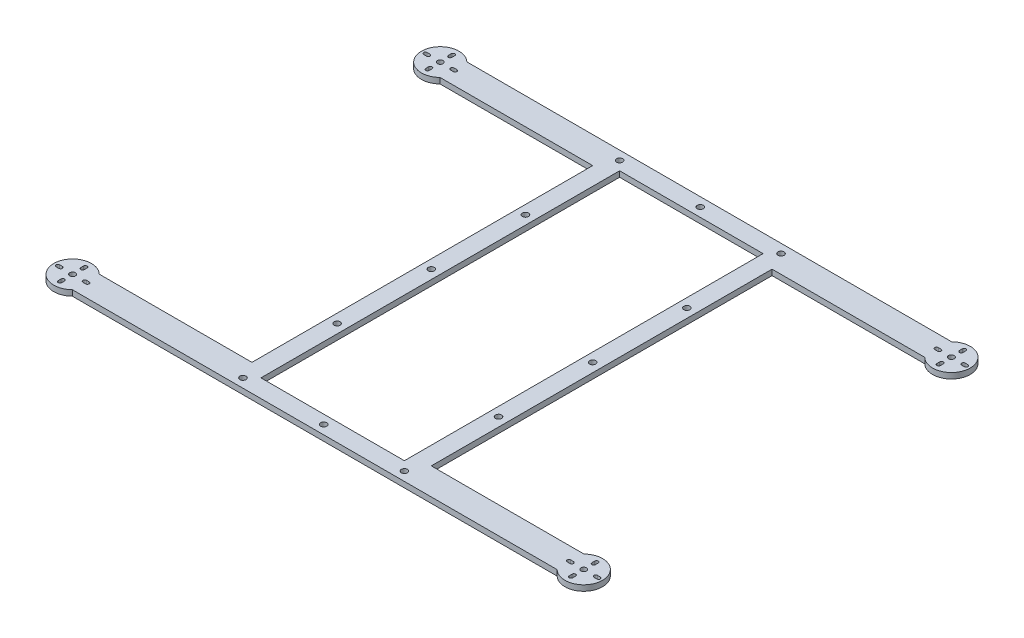
SolidWorks part; units mm, degrees
ref_plane "Front Plane" through (0, 0, 0) normal (0, 0, 1) x (1, 0, 0)
ref_plane "Top Plane" through (0, 0, 0) normal (0, 1, 0) x (1, 0, 0)
ref_plane "Right Plane" through (0, 0, 0) normal (1, 0, 0) x (0, 0, -1)
sketch "Sketch1" plane through (0, 0, 0) normal (0, 1, 0) x (1, 0, 0)
  line L1 (-63.5, 139.7) -> (63.5, 139.7)
  line L2 (-63.5, 120.65) -> (-63.5, -120.65)
  line L3 (-63.5, -139.7) -> (63.5, -139.7)
  line L4 (63.5, 120.65) -> (63.5, -120.65)
  line L5 (63.5, 139.7) -> (180.975, 139.7)
  line L7 (63.5, 120.65) -> (180.975, 120.65)
  line L8 (180.975, 139.7) -> (180.975, 120.65)
  line L14 (0, 0) -> (0, 187.5455) construction
  line L17 (0, 0) -> (-239.6804, 0) construction
  line L21 (0, 0) -> (63.5, 0) construction
  line L22 (-63.5, 120.65) -> (-180.975, 120.65)
  line L23 (-63.5, 139.7) -> (-180.975, 139.7)
  line L24 (-180.975, 139.7) -> (-180.975, 120.65)
  line L37 (-50.8, 127) -> (50.8, 127)
  line L40 (-50.8, 127) -> (-50.8, -127)
  line L43 (-50.8, -127) -> (50.8, -127)
  line L46 (50.8, 127) -> (50.8, -127)
  line L49 (63.5, -120.65) -> (180.975, -120.65)
  line L50 (63.5, -139.7) -> (180.975, -139.7)
  line L51 (180.975, -139.7) -> (180.975, -120.65)
  line L88 (-180.975, -139.7) -> (-180.975, -120.65)
  line L89 (-63.5, -139.7) -> (-180.975, -139.7)
  line L90 (-63.5, -120.65) -> (-180.975, -120.65)
  point P4 (0, 139.7)
  point P6 (-63.5, 0)
  dimension "D4" = 117.475
  dimension "D1" = 279.4
  dimension "D2" = 127
  dimension "D3" = 19.05
  dimension "D6" = 12.7
  dimension "D7" = 12.7
  dimension "D8" = 12.7
  dimension "D10" = 117.475
  dimension "D12" = 12.7
  dimension "D18" = 19.05
extrude "Boss-Extrude1" add sketch "Sketch1" along normal blind 4
sketch "Sketch4" plane through (0, 4, 0) normal (0, 1, 0) x (1, 0, 0)
  line L0 (180.975, 120.65) -> (180.975, 139.7) construction
  line L1 (-180.975, 139.7) -> (-180.975, 120.65) construction
  line L2 (-180.975, -120.65) -> (-180.975, -139.7) construction
  line L3 (180.975, -139.7) -> (180.975, -120.65) construction
  circle A0 centre (180.975, 130.175) radius 13.335
  circle A1 centre (-180.975, 130.175) radius 13.335
  circle A2 centre (-180.975, -130.175) radius 13.335
  circle A3 centre (180.975, -130.175) radius 13.335
  point P16 (180.975, -118.2416)
  point P17 (180.975, -105.2068)
  point P18 (180.975, -130.175)
extrude "Boss-Extrude4" add sketch "Sketch4" against normal up to surface (4 mm away) up to face at (0, 0, 0)
sketch "Sketch5" plane through (0, 4, 0) normal (0, 1, 0) x (1, 0, 0)
  line L0 (170.475, 130.175) -> (172.475, 130.175) construction
  line L1 (170.475, 131.425) -> (172.475, 131.425)
  line L2 (170.475, 128.925) -> (172.475, 128.925)
  line L3 (180.975, 130.175) -> (180.975, 143.51) construction
  line L4 (191.475, 130.175) -> (189.475, 130.175) construction
  line L5 (191.475, 131.425) -> (189.475, 131.425)
  line L6 (191.475, 128.925) -> (189.475, 128.925)
  line L7 (180.975, 139.175) -> (180.975, 137.175) construction
  line L8 (182.225, 139.175) -> (182.225, 137.175)
  line L9 (179.725, 139.175) -> (179.725, 137.175)
  line L10 (180.975, 130.175) -> (194.31, 130.175) construction
  line L11 (180.975, 121.175) -> (180.975, 123.175) construction
  line L12 (182.225, 121.175) -> (182.225, 123.175)
  line L13 (179.725, 121.175) -> (179.725, 123.175)
  line L14 (0, 0) -> (0, 263.0018) construction
  line L15 (0, 0) -> (558.7896, 0) construction
  line L16 (-170.475, 130.175) -> (-172.475, 130.175) construction
  line L17 (-170.475, 131.425) -> (-172.475, 131.425)
  line L18 (-170.475, 128.925) -> (-172.475, 128.925)
  line L19 (-191.475, 130.175) -> (-189.475, 130.175) construction
  line L20 (-191.475, 131.425) -> (-189.475, 131.425)
  line L21 (-191.475, 128.925) -> (-189.475, 128.925)
  line L22 (-180.975, 139.175) -> (-180.975, 137.175) construction
  line L23 (-182.225, 139.175) -> (-182.225, 137.175)
  line L24 (-179.725, 139.175) -> (-179.725, 137.175)
  line L25 (-180.975, 121.175) -> (-180.975, 123.175) construction
  line L26 (-182.225, 121.175) -> (-182.225, 123.175)
  line L27 (-179.725, 121.175) -> (-179.725, 123.175)
  line L28 (-180.975, 130.175) -> (-194.31, 130.175) construction
  line L29 (-180.975, 130.175) -> (-180.975, 143.51) construction
  line L30 (170.475, -130.175) -> (172.475, -130.175) construction
  line L31 (170.475, -131.425) -> (172.475, -131.425)
  line L32 (170.475, -128.925) -> (172.475, -128.925)
  line L33 (180.975, -139.175) -> (180.975, -137.175) construction
  line L34 (182.225, -139.175) -> (182.225, -137.175)
  line L35 (179.725, -139.175) -> (179.725, -137.175)
  line L36 (191.475, -130.175) -> (189.475, -130.175) construction
  line L37 (191.475, -131.425) -> (189.475, -131.425)
  line L38 (191.475, -128.925) -> (189.475, -128.925)
  line L39 (180.975, -121.175) -> (180.975, -123.175) construction
  line L40 (182.225, -121.175) -> (182.225, -123.175)
  line L41 (179.725, -121.175) -> (179.725, -123.175)
  line L42 (180.975, -130.175) -> (194.31, -130.175) construction
  line L43 (180.975, -130.175) -> (180.975, -143.51) construction
  line L44 (-180.975, -130.175) -> (-180.975, -143.51) construction
  line L45 (-180.975, -130.175) -> (-194.31, -130.175) construction
  line L46 (-180.975, -121.175) -> (-180.975, -123.175) construction
  line L47 (-182.225, -121.175) -> (-182.225, -123.175)
  line L48 (-179.725, -121.175) -> (-179.725, -123.175)
  line L49 (-180.975, -139.175) -> (-180.975, -137.175) construction
  line L50 (-182.225, -139.175) -> (-182.225, -137.175)
  line L51 (-179.725, -139.175) -> (-179.725, -137.175)
  line L52 (-191.475, -130.175) -> (-189.475, -130.175) construction
  line L53 (-191.475, -131.425) -> (-189.475, -131.425)
  line L54 (-191.475, -128.925) -> (-189.475, -128.925)
  line L55 (-170.475, -130.175) -> (-172.475, -130.175) construction
  line L56 (-170.475, -131.425) -> (-172.475, -131.425)
  line L57 (-170.475, -128.925) -> (-172.475, -128.925)
  circle A0 centre (180.975, 130.175) radius 2
  arc A1 (170.475, 131.425) -> (170.475, 128.925) centre (170.475, 130.175) ccw
  arc A2 (172.475, 128.925) -> (172.475, 131.425) centre (172.475, 130.175) ccw
  arc A3 (171.6424, 120.65) -> (171.6424, 139.7) centre (180.975, 130.175) ccw construction
  arc A4 (191.475, 131.425) -> (191.475, 128.925) centre (191.475, 130.175) cw
  arc A5 (189.475, 128.925) -> (189.475, 131.425) centre (189.475, 130.175) cw
  arc A6 (182.225, 139.175) -> (179.725, 139.175) centre (180.975, 139.175) ccw
  arc A7 (179.725, 137.175) -> (182.225, 137.175) centre (180.975, 137.175) ccw
  arc A8 (182.225, 121.175) -> (179.725, 121.175) centre (180.975, 121.175) cw
  arc A9 (179.725, 123.175) -> (182.225, 123.175) centre (180.975, 123.175) cw
  arc A10 (-170.475, 131.425) -> (-170.475, 128.925) centre (-170.475, 130.175) cw
  arc A11 (-172.475, 128.925) -> (-172.475, 131.425) centre (-172.475, 130.175) cw
  arc A12 (-191.475, 131.425) -> (-191.475, 128.925) centre (-191.475, 130.175) ccw
  arc A13 (-189.475, 128.925) -> (-189.475, 131.425) centre (-189.475, 130.175) ccw
  arc A14 (-182.225, 139.175) -> (-179.725, 139.175) centre (-180.975, 139.175) cw
  arc A15 (-179.725, 137.175) -> (-182.225, 137.175) centre (-180.975, 137.175) cw
  arc A16 (-182.225, 121.175) -> (-179.725, 121.175) centre (-180.975, 121.175) ccw
  arc A17 (-179.725, 123.175) -> (-182.225, 123.175) centre (-180.975, 123.175) ccw
  circle A18 centre (-180.975, 130.175) radius 2
  arc A19 (170.475, -131.425) -> (170.475, -128.925) centre (170.475, -130.175) cw
  arc A20 (172.475, -128.925) -> (172.475, -131.425) centre (172.475, -130.175) cw
  arc A21 (182.225, -139.175) -> (179.725, -139.175) centre (180.975, -139.175) cw
  arc A22 (179.725, -137.175) -> (182.225, -137.175) centre (180.975, -137.175) cw
  arc A23 (191.475, -131.425) -> (191.475, -128.925) centre (191.475, -130.175) ccw
  arc A24 (189.475, -128.925) -> (189.475, -131.425) centre (189.475, -130.175) ccw
  arc A25 (182.225, -121.175) -> (179.725, -121.175) centre (180.975, -121.175) ccw
  arc A26 (179.725, -123.175) -> (182.225, -123.175) centre (180.975, -123.175) ccw
  circle A27 centre (180.975, -130.175) radius 2
  circle A28 centre (-180.975, -130.175) radius 2
  arc A29 (-182.225, -121.175) -> (-179.725, -121.175) centre (-180.975, -121.175) cw
  arc A30 (-179.725, -123.175) -> (-182.225, -123.175) centre (-180.975, -123.175) cw
  arc A31 (-182.225, -139.175) -> (-179.725, -139.175) centre (-180.975, -139.175) ccw
  arc A32 (-179.725, -137.175) -> (-182.225, -137.175) centre (-180.975, -137.175) ccw
  arc A33 (-191.475, -131.425) -> (-191.475, -128.925) centre (-191.475, -130.175) cw
  arc A34 (-189.475, -128.925) -> (-189.475, -131.425) centre (-189.475, -130.175) cw
  arc A35 (-170.475, -131.425) -> (-170.475, -128.925) centre (-170.475, -130.175) ccw
  arc A36 (-172.475, -128.925) -> (-172.475, -131.425) centre (-172.475, -130.175) ccw
  point P5 (171.475, 130.175)
  point P16 (190.475, 130.175)
  point P23 (180.975, 138.175)
  point P31 (180.975, 122.175)
  point P42 (-171.475, 130.175)
  point P49 (-190.475, 130.175)
  point P56 (-180.975, 138.175)
  point P63 (-180.975, 122.175)
  point P74 (171.475, -130.175)
  point P81 (180.975, -138.175)
  point P88 (190.475, -130.175)
  point P95 (180.975, -122.175)
  point P110 (-180.975, -122.175)
  point P117 (-180.975, -138.175)
  point P124 (-190.475, -130.175)
  point P131 (-171.475, -130.175)
  dimension "D1" = 4
  dimension "D2" = 2.5
  dimension "D3" = 2
  dimension "D4" = 9.5
  dimension "D5" = 2.5
  dimension "D6" = 2
  dimension "D7" = 8
extrude "Motor Holes" cut sketch "Sketch5" against normal through all
sketch "Sketch7" plane through (0, 4, 0) normal (0, 1, 0) x (1, 0, 0)
  line L0 (171.6424, 139.7) -> (-171.6424, 139.7) construction
  line L1 (-63.5, 120.65) -> (-63.5, -120.65) construction
  line L2 (0, 0) -> (0, 246.0772) construction
  line L3 (0, 0) -> (301.4392, 0) construction
  circle A0 centre (-57.15, 133.35) radius 2.159
  circle A1 centre (-57.15, 66.675) radius 2.159
  circle A2 centre (-57.15, 0) radius 2.159
  circle A3 centre (-57.15, -66.675) radius 2.159
  circle A5 centre (-57.15, -133.35) radius 2.159
  circle A6 centre (57.15, -133.35) radius 2.159
  circle A7 centre (57.15, -66.675) radius 2.159
  circle A8 centre (57.15, 0) radius 2.159
  circle A9 centre (57.15, 66.675) radius 2.159
  circle A10 centre (57.15, 133.35) radius 2.159
  circle A11 centre (0, 133.35) radius 2.159
  circle A12 centre (0, -133.35) radius 2.159
  point P30 (0, 133.35)
  dimension "D1" = 4.318
  dimension "D2" = 6.35
  dimension "D3" = 6.35
  dimension "D4" = 66.675
  dimension "D5" = 66.675
  dimension "D6" = 66.675
  dimension "D7" = 66.675
extrude "Cut-Extrude2" cut sketch "Sketch7" against normal through all
